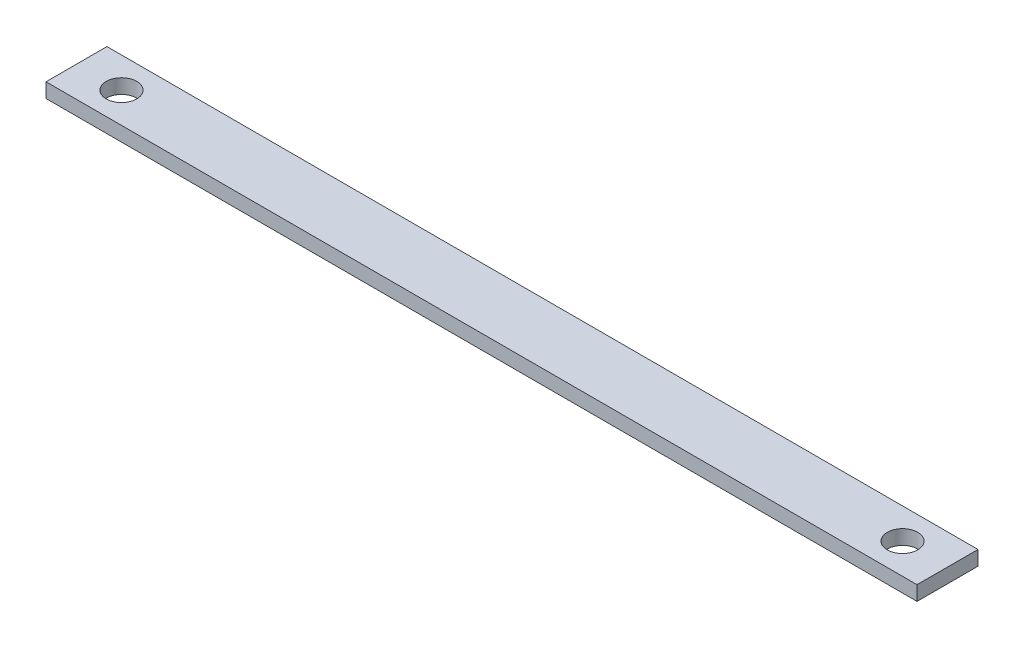
SolidWorks part; units mm, degrees
ref_plane "Plan de face" through (0, 0, 0) normal (0, 0, 1) x (1, 0, 0)
ref_plane "Plan de dessus" through (0, 0, 0) normal (0, 1, 0) x (1, 0, 0)
ref_plane "Plan de droite" through (0, 0, 0) normal (1, 0, 0) x (0, 0, -1)
sketch "Esquisse1" plane through (0, 0, 0) normal (0, 1, 0) x (1, 0, 0)
  line L1 (-300, -21) -> (300, -21)
  line L2 (-300, -21) -> (-300, 21)
  line L3 (-300, 21) -> (300, 21)
  line L4 (300, -21) -> (300, 21)
  line L5 (-300, -21) -> (300, 21) construction
  line L6 (-300, 21) -> (300, -21) construction
  point P0 (0, 0)
  dimension "D1" = 600
  dimension "D2" = 42
extrude "Boss.-Extru.1" add sketch "Esquisse1" along normal blind 10
sketch "Esquisse2" plane through (0, 10, 0) normal (0, 1, 0) x (1, 0, 0)
  line L0 (-238, 0) -> (-300, 0) construction
  line L1 (-300, -21) -> (300, -21) construction
  line L2 (-238, -21) -> (-238, 21) construction
  line L3 (300, 21) -> (-300, 21) construction
  line L4 (-238, 21) -> (-300, 21) construction
  line L5 (238, 21) -> (238, -21) construction
  line L6 (198, -21) -> (300, -21) construction
  line L7 (300, -21) -> (300, 21) construction
  line L8 (-300, 21) -> (-300, -21) construction
  line L9 (238, 0) -> (300, 0) construction
  circle A2 centre (-269, 0) radius 10.5
  circle A3 centre (269, 0) radius 10.5
  dimension "D1" = 21
  dimension "D2" = 62
  dimension "D4" = 21
  dimension "D3" = 62
extrude "Enlèv. mat.-Extru.1" cut sketch "Esquisse2" against normal blind 20
